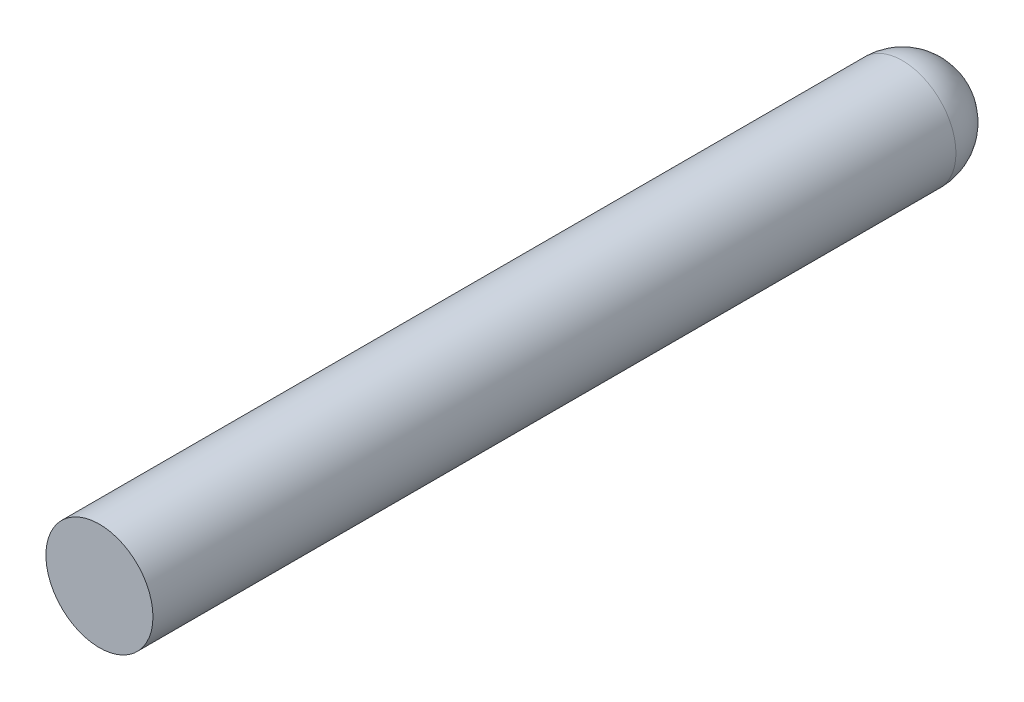
SolidWorks part; units mm, degrees
ref_plane "Front Plane" through (0, 0, 0) normal (0, 0, 1) x (1, 0, 0)
ref_plane "Top Plane" through (0, 0, 0) normal (0, 1, 0) x (1, 0, 0)
ref_plane "Right Plane" through (0, 0, 0) normal (1, 0, 0) x (0, 0, -1)
sketch "Sketch1" plane through (0, 0, 0) normal (0, 0, 1) x (1, 0, 0)
  circle A0 centre (0, 0) radius 25.4
extrude "Boss-Extrude3" add sketch "Sketch1" along normal blind 381
sketch "Sketch4" plane through (0, 0, 0) normal (0, 1, 0) x (1, 0, 0)
  line L0 (25.4, 0) -> (-25.4, 0) construction
  line L1 (0, 0) -> (0, 25.4) construction
  line L2 (-25.4, 0) -> (25.4, 0)
  arc A0 (-25.4, 0) -> (25.4, 0) centre (0, 0) cw
revolve "Revolve3" add sketch "Sketch4" angle 360 about L1 region at (-10.7801, 0, -10.7801)
